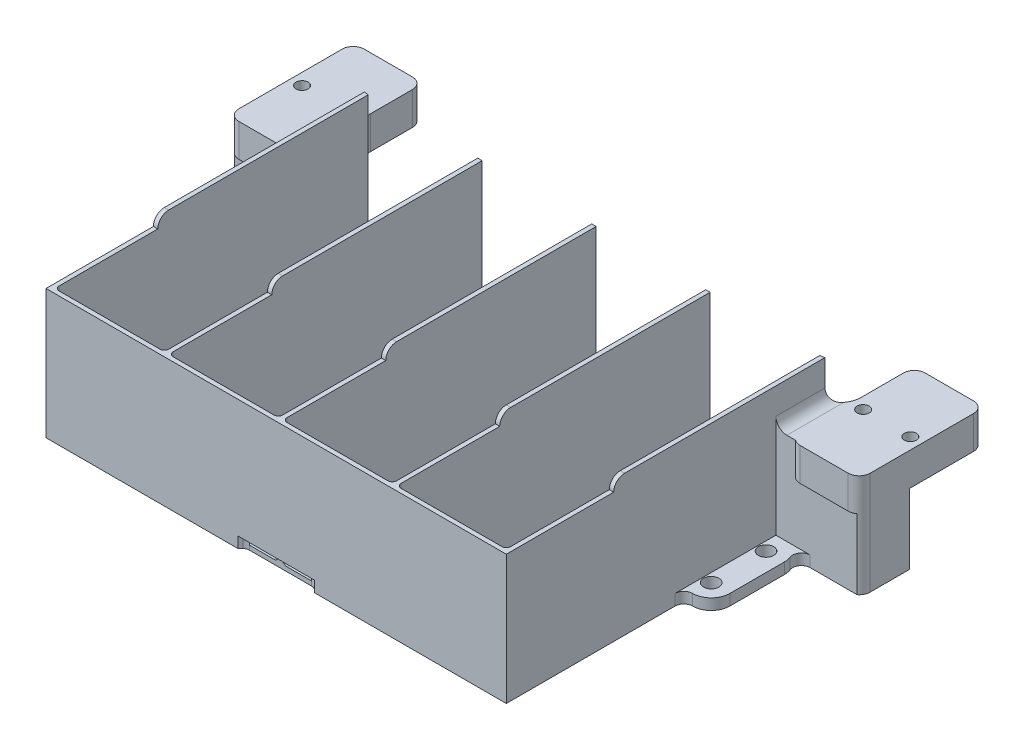
SolidWorks part; units mm, degrees
material "ПК/АБС"
ref_plane "Спереди" through (0, 0, 0) normal (0, 0, 1) x (1, 0, 0)
ref_plane "Сверху" through (0, 0, 0) normal (0, 1, 0) x (1, 0, 0)
ref_plane "Справа" through (0, 0, 0) normal (1, 0, 0) x (0, 0, -1)
sketch "Эскиз2" plane through (0, 0, 0) normal (0, 0, 1) x (1, 0, 0)
  line L1 (0, 0) -> (44, 0) construction
  line L2 (0, 0) -> (0, 57) construction
  line L3 (0, 57) -> (44, 57) construction
  line L4 (44, 0) -> (44, 57) construction
  line L5 (47, -3) -> (47, 60)
  line L7 (-3, -3) -> (-3, 60)
  line L8 (48, -3) -> (48, 60) construction
  line L9 (52, 0) -> (52, 57) construction
  line L10 (96, 57) -> (52, 57) construction
  line L11 (96, 0) -> (96, 57) construction
  line L12 (96, 0) -> (52, 0) construction
  line L13 (99, -3) -> (99, 60)
  line L15 (49, -3) -> (49, 60)
  line L17 (100, -3) -> (100, 60) construction
  line L18 (104, 0) -> (148, 0) construction
  line L19 (104, 0) -> (104, 57) construction
  line L20 (104, 57) -> (148, 57) construction
  line L21 (148, 0) -> (148, 57) construction
  line L22 (156, 0) -> (156, 57) construction
  line L23 (200, 57) -> (156, 57) construction
  line L24 (200, 0) -> (200, 57) construction
  line L25 (200, 0) -> (156, 0) construction
  line L27 (151, -3) -> (151, 60)
  line L29 (101, -3) -> (101, 60)
  line L30 (152, -3) -> (152, 60) construction
  line L31 (203, -3) -> (203, 60)
  line L33 (153, -3) -> (153, 60)
  line L35 (-3, 60) -> (47, 60) construction
  line L36 (-3, 60) -> (47, 60)
  line L37 (-3, -3) -> (47, -3)
  line L38 (-3, -3) -> (47, -3) construction
  line L39 (-5, 62) -> (205, 62)
  line L40 (205, -5) -> (205, 62)
  line L41 (-5, -5) -> (205, -5)
  line L42 (-5, -5) -> (-5, 62)
  line L43 (49, 60) -> (99, 60)
  line L44 (-3, 60) -> (203, 60) construction
  line L45 (49, -3) -> (99, -3)
  line L46 (-3, -3) -> (203, -3) construction
  line L47 (101, -3) -> (151, -3)
  line L48 (101, 60) -> (151, 60)
  line L49 (153, 60) -> (203, 60)
  line L50 (153, -3) -> (203, -3)
  dimension "D1" = 44
  dimension "D2" = 57
  dimension "D3" = 3
  dimension "D4" = 1
  dimension "D5" = 1
  dimension "D6" = 2
extrude "Бобышка-Вытянуть1" add sketch "Эскиз2" along normal blind 143
sketch "Эскиз3" plane through (0, 0, 143) normal (0, 0, 1) x (1, 0, 0)
  line L1 (-5, 62) -> (205, 62)
  line L2 (-5, 62) -> (-5, -5)
  line L3 (-5, -5) -> (205, -5)
  line L4 (205, 62) -> (205, -5)
extrude "Бобышка-Вытянуть2" add sketch "Эскиз3" along normal blind 2
sketch "Эскиз4" plane through (0, -5, 0) normal (0, -1, 0) x (1, 0, 0)
  line L24 (116, 145) -> (84, 145) construction
  line L26 (85.8284, 143) -> (114.1716, 143)
  line L27 (116.2929, 143.8787) -> (118.4142, 146)
  line L28 (118.4142, 146) -> (81.5858, 146)
  line L29 (81.5858, 146) -> (83.7071, 143.8787)
  line L36 (85.8284, 144) -> (114.1716, 144) construction
  line L37 (115.5858, 144.5858) -> (116, 145) construction
  line L47 (84, 145) -> (84.4142, 144.5858) construction
  arc A12 (114.1716, 143) -> (116.2929, 143.8787) centre (114.1716, 146) ccw
  arc A13 (83.7071, 143.8787) -> (85.8284, 143) centre (85.8284, 146) ccw
  arc A18 (114.1716, 144) -> (115.5858, 144.5858) centre (114.1716, 146) ccw construction
  arc A23 (84.4142, 144.5858) -> (85.8284, 144) centre (85.8284, 146) ccw construction
  dimension "D1" = 1
extrude "Вырез-Вытянуть1" cut sketch "Эскиз4" against normal blind 5
sketch "Эскиз5" plane through (0, 62, 0) normal (0, 1, 0) x (1, 0, 0)
  line L1 (-5, 0) -> (205, 0)
  line L2 (-5, 0) -> (-5, -145)
  line L3 (-5, -145) -> (205, -145)
  line L4 (205, 0) -> (205, -145)
extrude "Вырез-Вытянуть2" cut sketch "Эскиз5" against normal blind 3
sketch "Эскиз6" plane through (0, -5, 0) normal (0, -1, 0) x (1, 0, 0)
  line L0 (205, 22) -> (205, 39)
  line L2 (209, 22) -> (205, 22)
  line L3 (209, 39) -> (205, 39)
  line L4 (209, 47) -> (205, 47)
  line L5 (209, 64) -> (205, 64)
  line L6 (205, 47) -> (205, 64)
  line L7 (100, 0) -> (100, 13.217) construction
  line L8 (101, 0) -> (99, 0) construction
  line L9 (-5, 47) -> (-5, 64)
  line L10 (-9, 64) -> (-5, 64)
  line L11 (-9, 47) -> (-5, 47)
  line L12 (-9, 39) -> (-5, 39)
  line L13 (-9, 22) -> (-5, 22)
  line L14 (-5, 22) -> (-5, 39)
  circle A0 centre (209, 30.5) radius 3.5
  circle A1 centre (209, 55.5) radius 3.5
  arc A2 (209, 22) -> (209, 39) centre (209, 30.5) ccw
  arc A3 (209, 47) -> (209, 64) centre (209, 55.5) ccw
  circle A4 centre (209, 55.5) radius 8.5 construction
  circle A5 centre (209, 30.5) radius 8.5 construction
  arc A6 (-9, 47) -> (-9, 64) centre (-9, 55.5) cw
  arc A7 (-9, 22) -> (-9, 39) centre (-9, 30.5) cw
  circle A8 centre (-9, 55.5) radius 3.5
  circle A9 centre (-9, 30.5) radius 3.5
  dimension "D1" = 5
extrude "Бобышка-Вытянуть3" add sketch "Эскиз6" against normal blind 5
sketch "Эскиз7" plane through (0, -5, 0) normal (0, -1, 0) x (1, 0, 0)
  line L0 (205, 22) -> (205, 0) construction
  line L1 (205, 22) -> (244, 22)
  line L2 (205, 22) -> (205, 0)
  line L3 (205, 0) -> (244, 0)
  line L4 (244, 22) -> (244, 0)
extrude "Бобышка-Вытянуть4" add sketch "Эскиз7" against normal up to surface (47 mm away)
sketch "Эскиз8" plane through (0, 42, 0) normal (0, -1, 0) x (1, 0, 0)
  line L12 (239, 23) -> (217, 23)
  line L13 (212, 18) -> (212, -29.15)
  line L14 (217, -34.15) -> (239, -34.15)
  line L15 (244, -29.15) -> (244, 18)
  circle A8 centre (238.75, -5.575) radius 2.75
  circle A9 centre (217.25, -5.575) radius 2.75
  arc A12 (244, 18) -> (239, 23) centre (239, 18) ccw
  arc A13 (217, 23) -> (212, 18) centre (217, 18) ccw
  arc A14 (212, -29.15) -> (217, -34.15) centre (217, -29.15) ccw
  arc A15 (239, -34.15) -> (244, -29.15) centre (239, -29.15) ccw
extrude "Бобышка-Вытянуть5" add sketch "Эскиз8" along normal blind 15
sketch "Эскиз9" plane through (0, 42, 0) normal (0, 1, 0) x (1, 0, 0)
  line L0 (212, 5.575) -> (244, 5.575) construction
  line L9 (239, -23) -> (235.2742, -23)
  line L10 (235.2742, -23) -> (246.5968, -31.7099)
  line L11 (246.5968, -31.7099) -> (255.6971, -21.5514)
  line L12 (255.6971, -21.5514) -> (244, -13.4034)
  line L28 (244, -18) -> (244, -13.4034)
  arc A5 (244, -18) -> (239, -23) centre (239, -18) cw
extrude "Вырез-Вытянуть3" cut sketch "Эскиз9" against normal through all
fillet "Скругление1" radius 10 1 edges at (212, 34.5, 0)
fillet "Скругление2" radius 4 4 edges at (209, -2.5, 22) (205, -2.5, 64) (205, -2.5, 47) (205, -2.5, 39)
sketch "Эскиз10" plane through (0, 0, 0) normal (0, 1, 0) x (1, 0, 0)
  line L0 (217.5, -30.5) -> (217.5, -55.5)
  line L1 (217.5, -55.5) -> (206.0609, -47)
  line L2 (206.0609, -47) -> (205, -45.9391)
  line L3 (205, -68) -> (205, -43) construction
  line L4 (205, -45.9391) -> (205, -34.5792)
  line L5 (205, -145) -> (205, 0.4105) construction
  line L6 (205, -34.5792) -> (213.2954, -34.5792)
  line L7 (213.2954, -34.5792) -> (217.5, -30.5)
  arc A0 (209, -39) -> (216.9301, -27.44) centre (209, -30.5) ccw construction
  arc A1 (209, -64) -> (209, -47) centre (209, -55.5) ccw construction
extrude "Бобышка-Вытянуть6" add sketch "Эскиз10" against normal up to surface (5 mm away) up to face at (108.6922, -5, 68.4551)
ref_plane "Плоскость4" through (100, 0, 0) normal (1, 0, 0) x (0, 0, -1)
mirror "Зеркальное отражение1" about plane through (100, 0, 0) normal (1, 0, 0) of bodies 109
fillet "Скругление3" radius 5 2 edges at (205, 42, 10.7948) (-5, 42, 10.7948)
fillet "Скругление4" radius 2 18 edges at (203, -3, 71.5) (178, -3, 143) (153, -3, 71.5) (203, 28, 143) (153, 28, 143) (151, 28, 143) (151, -3, 71.5) (101, -3, 71.5) (101, 29.5, 143) (99, 29.5, 143) (49, 28, 143) (-3, 28, 143) (-3, -3, 71.5) (47, 28, 143) (22, -3, 143) (47, -3, 71.5) (49, -3, 71.5) (99, -3, 71.5)
sketch "Эскиз11" plane through (0, 59, 0) normal (0, 1, 0) x (1, 0, 0)
  line L0 (205, -145) -> (205, 0.4105) construction
  line L1 (-5, -145) -> (205, -145)
  line L2 (-5, -145) -> (-5, -96)
  line L3 (-5, -96) -> (205, -96)
  line L4 (205, -145) -> (205, -96)
  dimension "D1" = 49
extrude "Вырез-Вытянуть4" cut sketch "Эскиз11" against normal blind 5
fillet "Скругление5" radius 5 2 edges at (48, 59, 96) (152, 59, 96)
